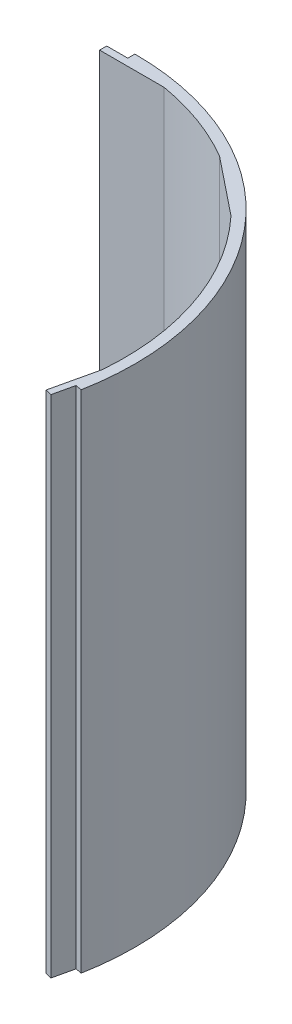
SolidWorks part; units mm, degrees
ref_plane "Спереди" through (0, 0, 0) normal (0, 0, 1) x (1, 0, 0)
ref_plane "Сверху" through (0, 0, 0) normal (0, 1, 0) x (1, 0, 0)
ref_plane "Справа" through (0, 0, 0) normal (1, 0, 0) x (0, 0, -1)
sketch "Эскиз2" plane through (0, 0, 0) normal (0, 1, 0) x (1, 0, 0)
  line L0 (0, -1000) -> (0, 49000) construction
  line L1 (-8.2529, 48.3) -> (8.2529, 48.3) construction
  line L2 (35.7629, 33.4965) -> (24.8621, 42.2241) construction
  line L3 (48.839, -3.9694) -> (45.736, -17.5845) construction
  line L4 (-4, 48.3) -> (8.2529, 48.3)
  line L5 (35.7629, 33.4965) -> (24.8621, 42.2241)
  line L6 (48.839, -3.9694) -> (45.736, -17.5845) construction
  line L7 (-4, 48.3) -> (-4, 49.65)
  line L8 (-4, 49.65) -> (0, 49.65)
  line L10 (-8.2529, 48.3) -> (-4, 48.3) construction
  line L12 (0, 0) -> (47.2875, -10.7769) construction
  line L13 (50.1312, -9.3737) -> (48.9507, -9.1047)
  line L14 (48.9507, -9.1047) -> (48.0618, -13.0047)
  line L15 (48.0618, -13.0047) -> (46.8431, -12.7269)
  line L16 (47.2875, -10.7769) -> (49.725, -11.3324) construction
  line L17 (46.8431, -12.7269) -> (48.839, -3.9694)
  line L19 (0, 49.65) -> (0, 51)
  line L20 (0, 48.3) -> (0, 49.65) construction
  circle A0 centre (0, 0) radius 51 construction
  arc A1 (50.1312, -9.3737) -> (0, 51) centre (0, 0) ccw
  circle A2 centre (0, 0) radius 51 construction
  arc A3 (48.839, -3.9694) -> (35.7629, 33.4965) centre (0, 0) ccw construction
  arc A4 (0, 51) -> (0, -51) centre (0, 0) ccw construction
  arc A5 (48.839, -3.9694) -> (35.7629, 33.4965) centre (0, 0) ccw
  arc A6 (8.2529, 48.3) -> (24.8621, 42.2241) centre (0, 0) cw
  arc A7 (0, -51) -> (49.725, -11.3324) centre (0, 0) ccw construction
  arc A8 (49.725, -11.3324) -> (50.1312, -9.3737) centre (0, 0) ccw construction
  point P25 (48.5063, -11.0547)
  dimension "D1" = 4
extrude "Бобышка-Вытянуть2" add sketch "Эскиз2" along normal up to surface (96 mm away)
ref_plane "Плоскость4" through (12.7171, 0, -36.1271) normal (-0.332, 0, 0.9433) x (0.9433, 0, 0.332)
sketch "Эскиз7" plane through (12.7171, 0, -36.1271) normal (-0.332, 0, 0.9433) x (0.9433, 0, 0.332)
  line L5 (-8.2529, 17) -> (5.2529, 17) construction
  line L6 (-8.2529, 17) -> (5.2529, 17) construction
  line L7 (8.2529, 14) -> (5.2529, 17) construction
  line L8 (8.2529, 14) -> (5.2529, 17)
  line L9 (-8.2529, 0) -> (8.2529, 0) construction
  line L16 (-8.2529, 0) -> (8.2529, 0)
  line L17 (-8.2529, 96) -> (-8.2529, 0) construction
  line L18 (-8.2529, 17) -> (-8.2529, 0) construction
  line L19 (8.7529, 14.2071) -> (8.7529, 0)
  line L20 (8.7529, 14.2071) -> (5.46, 17.5)
  line L21 (8.2529, 14) -> (8.2529, 0) construction
  line L22 (8.2529, 14) -> (8.2529, 0) construction
  line L23 (-8.7529, 17.5) -> (5.46, 17.5)
  line L24 (-8.7529, 17.5) -> (-8.7529, 0)
  line L25 (-8.7529, 0) -> (-8.2529, 0)
  line L26 (8.2529, 0) -> (8.7529, 0)
  dimension "D1" = 0.5
extrude "Вырез-Вытянуть3" cut sketch "Эскиз7" against normal through all contours L16 L26 L19 L20 L23 L24 L25 region at (12.587, 8.6121, -36.1729)
sketch "Эскиз9" plane through (0, 0, -48.3) normal (0, 0, 1) x (1, 0, 0)
  line L4 (8.7529, 0) -> (8.7529, 17.5)
  line L6 (-4, 96) -> (-4, 0) construction
  line L7 (-4, 19.5) -> (-4, 0)
  line L8 (-4, 96) -> (-4, 19.5) construction
  line L9 (-4, 19.5) -> (-6.5, 17) construction
  line L10 (-8.2529, 0) -> (-4, 0) construction
  line L11 (8.7529, 17.5) -> (6.7071, 17.5)
  line L12 (6.7071, 17.5) -> (3.7071, 20.5)
  line L13 (3.7071, 20.5) -> (-3.7071, 20.5)
  line L14 (-8.2529, 0) -> (8.2529, 0)
  line L15 (8.2529, 0) -> (8.2529, 17)
  line L24 (8.2529, 17) -> (6.5, 17)
  line L25 (6.5, 17) -> (3.5, 20)
  line L26 (3.5, 20) -> (-3.5, 20)
  line L28 (-3.7071, 20.5) -> (-4, 20.2071)
  line L29 (-3.5, 20) -> (-6.5, 17)
  line L30 (-6.5, 17) -> (-8.2529, 17)
  line L31 (-8.2529, 17) -> (-8.2529, 0)
  line L32 (-4, 0) -> (8.2529, 0)
  line L33 (8.2529, 0) -> (8.2529, 17) construction
  line L34 (8.2529, 17) -> (6.5, 17) construction
  line L35 (6.5, 17) -> (3.5, 20) construction
  line L36 (3.5, 20) -> (-3.5, 20) construction
  line L37 (-3.5, 20) -> (-4, 19.5)
  line L38 (-6.5, 17) -> (-8.2529, 17) construction
  line L39 (-8.2529, 17) -> (-8.2529, 0) construction
  line L40 (-4, 19.5) -> (-4, 20.2071)
  line L41 (-4, 20.2071) -> (-4.3536, 19.8536) construction
  line L42 (-3.7071, 20.5) -> (-4.3536, 19.8536) construction
  line L43 (8.7529, 0) -> (8.2529, 0)
  line M9 (-8.2529, 0) -> (8.2529, 0)
  line M10 (8.2529, 0) -> (8.2529, 17)
  line M11 (8.2529, 17) -> (6.5, 17)
  line M12 (6.5, 17) -> (3.5, 20)
  line M13 (3.5, 20) -> (-3.5, 20)
  line M14 (-3.5, 20) -> (-6.5, 17)
  dimension "D1" = 0
  dimension "D2" = 0.5
extrude "Вырез-Вытянуть4" cut sketch "Эскиз9" against normal through all contours L7 M14 M9 M10 M11 M12 M13 | L43 L4 L11 L12 L13 L28 L40 M14 M13 M12 M11 M10 region at (8.5029, 0.2414, -48.3) region at (1.9477, 9.6325, -48.3)
sketch "Эскиз10" plane through (0, 12, 0) normal (0, 1, 0) x (1, 0, 0)
  line L0 (-4, 48.3) -> (8.2529, 48.3) construction
  line L1 (-4, 48.3) -> (8.2529, 48.3)
  line L2 (23.8222, 42.8194) -> (20.9924, 43.8155) construction
  line L3 (8.2529, 48.3) -> (20.9924, 43.8155) construction
  line L4 (23.8222, 42.8194) -> (20.9924, 43.8155)
  line L5 (8.2529, 48.3) -> (20.9924, 43.8155)
  line L7 (23.4097, 41.9045) -> (20.6603, 42.8723)
  line L8 (8.082, 47.3) -> (20.6603, 42.8723)
  line L9 (-4, 47.3) -> (8.082, 47.3)
  line L10 (-4, 47.3) -> (-4, 48.3)
  line L11 (24.3547, 41.3624) -> (24.8621, 42.2241) construction
  line L12 (24.3547, 41.3624) -> (26.3116, 41.0636)
  line L13 (24.8621, 42.2241) -> (35.7629, 33.4965) construction
  line L14 (26.3116, 41.0636) -> (24.8621, 42.2241) construction
  line L15 (26.3116, 41.0636) -> (24.8621, 42.2241) construction
  line L16 (26.3116, 41.0636) -> (24.8621, 42.2241)
  arc A0 (24.8621, 42.2241) -> (8.2529, 48.3) centre (0, 0) ccw construction
  arc A1 (24.8621, 42.2241) -> (23.8222, 42.8194) centre (0, 0) ccw
  arc A2 (23.8222, 42.8194) -> (8.2529, 48.3) centre (0, 0) ccw construction
  arc A3 (24.3547, 41.3624) -> (23.4097, 41.9045) centre (0, 0) ccw
  dimension "D2" = 30
  dimension "D1" = 1
extrude "Бобышка-Вытянуть7" add sketch "Эскиз10" along normal blind 10
chamfer "Фаска4" distance 1 angle 45 3 edges at (2.041, 22, -47.3) (23.8837, 22, -41.6361) (15.7459, 22, -44.6022)
